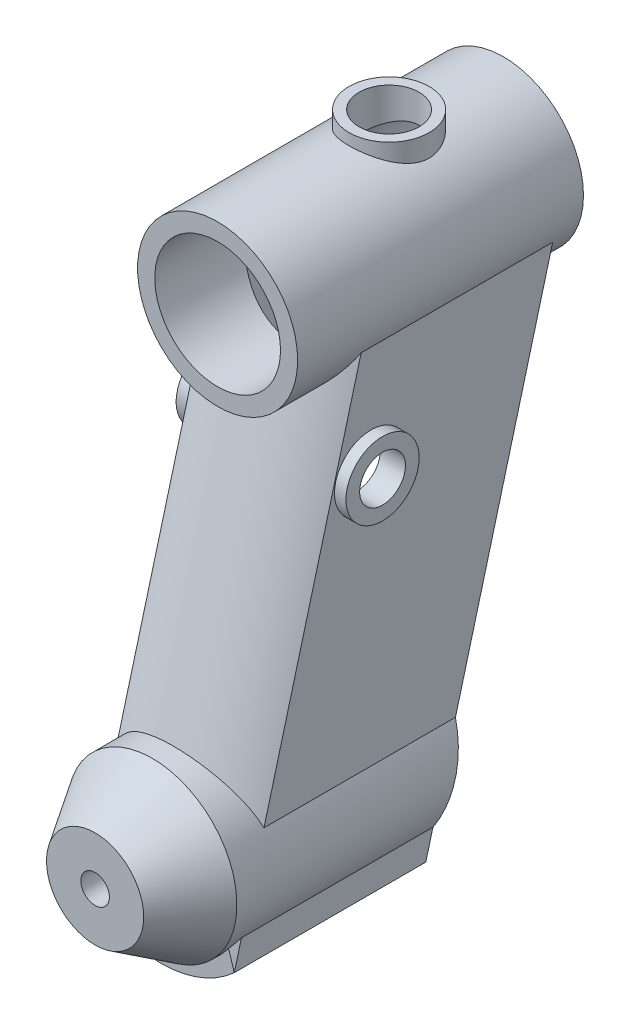
SolidWorks part; units mm, degrees
ref_plane "Front Plane" through (0, 0, 0) normal (0, 0, 1) x (1, 0, 0)
ref_plane "Top Plane" through (0, 0, 0) normal (0, 1, 0) x (1, 0, 0)
ref_plane "Right Plane" through (0, 0, 0) normal (1, 0, 0) x (0, 0, -1)
sketch "Sketch1" plane through (0, 0, 0) normal (0, 0, 1) x (1, 0, 0)
  circle A0 centre (0, 0) radius 14
  circle A1 centre (0, 0) radius 11
  dimension "D1" = 28
  dimension "D2" = 22
extrude "Boss-Extrude1" add sketch "Sketch1" along normal blind 25 and the other way blind 25
sketch "Sketch2" plane through (0, 0, 0) normal (1, 0, 0) x (0, 0, -1)
  line L0 (-25, -14) -> (25, -14) construction
  line L1 (-25, -14) -> (25, -14) construction
  line L2 (-15, -14) -> (-34.9291, -88.3763)
  line L3 (18.5, -14) -> (-1.4291, -88.3763)
  line L4 (18.5, -14) -> (18.5, -88.3763) construction
  line L5 (18.5, -88.3763) -> (-1.4291, -88.3763) construction
  line L6 (-34.9291, -88.3763) -> (-1.4291, -88.3763)
  line L7 (-15, -14) -> (18.5, -14) construction
  line L8 (-15, -14) -> (-11.2487, 0)
  line L9 (-11.2487, 0) -> (22.2513, 0)
  line L10 (22.2513, 0) -> (18.5, -14)
  dimension "D1" = 10
  dimension "D2" = 33.5
  dimension "D3" = 15
  dimension "D4" = 77
extrude "Boss-Extrude2" add sketch "Sketch2" along normal blind 12.85 and the other way blind 12.85
sketch "Sketch3" plane through (0, -88.3763, 0) normal (0, -1, 0) x (1, 0, 0)
  line L0 (-12.85, 34.9291) -> (12.85, 34.9291) construction
  line L1 (0, 34.9291) -> (0, 39.9291) construction
  line L2 (-12.85, 34.9291) -> (12.85, 34.9291)
  arc A0 (-12.85, 34.9291) -> (12.85, 34.9291) centre (0, 20.9168) cw
  dimension "D1" = 5
extrude "Boss-Extrude3" add sketch "Sketch3" along direction (0, -0.9659, 0.2588) on the side against the normal up to surface (85.7411 mm away) up to face at (0, -9.7784, -2.8812)
ref_plane "Plane1" through (0, 0, 1.4291) normal (0, 0, 1) x (1, 0, 0)
sketch "Sketch4" plane through (0, 0, 1.4291) normal (0, 0, 1) x (1, 0, 0)
  line L0 (-12.85, -88.3763) -> (12.85, -88.3763) construction
  line L1 (-12.85, -88.3763) -> (12.85, -88.3763)
  line L2 (0, -88.3763) -> (0, -93.3763) construction
  arc A0 (-12.85, -88.3763) -> (12.85, -88.3763) centre (0, -74.364) ccw
  dimension "D1" = 5
extrude "Boss-Extrude4" add sketch "Sketch4" along normal up to vertex (33.5 mm away) up to point (-12.85, -88.3763, 34.9291)
sketch "Sketch6" plane through (0, 0, 1.4291) normal (0, 0, 1) x (1, 0, 0)
  line L0 (0, -93.3763) -> (0, -74.364) construction
  arc A0 (-12.85, -88.3763) -> (12.85, -88.3763) centre (0, -74.364) ccw construction
  arc A1 (-12.85, -88.3763) -> (12.85, -88.3763) centre (0, -74.364) ccw construction
  circle A2 centre (0, -76.364) radius 14.8
  point P6 (0, -76.3948)
  point P7 (0, 0)
  dimension "D1" = 29.6
  dimension "D2" = 2
extrude "Boss-Extrude5" add sketch "Sketch6" along normal blind 35
sketch "Sketch7" plane through (0, 0, 36.4291) normal (0, 0, 1) x (1, 0, 0)
  arc A0 (10.4067, -86.8874) -> (-10.4067, -86.8874) centre (0, -76.364) ccw construction
  arc A1 (10.4067, -86.8874) -> (-10.4067, -86.8874) centre (0, -76.364) ccw construction
  circle A2 centre (0, -76.364) radius 14.8
extrude "Cut-Extrude2" cut sketch "Sketch7" along normal through all
sketch "Sketch10" plane through (0, 0, 34.9291) normal (0, 0, 1) x (1, 0, 0)
  line L0 (-12.85, -83.7069) -> (-12.85, -88.3763)
  line L1 (12.85, -83.7069) -> (12.85, -88.3763)
  arc A0 (10.4067, -86.8874) -> (-10.4067, -86.8874) centre (0, -76.364) ccw construction
  arc A1 (10.4067, -86.8874) -> (12.85, -83.7069) centre (0, -76.364) ccw
  arc A2 (-12.85, -88.3763) -> (12.85, -88.3763) centre (0, -74.364) ccw construction
  arc A3 (-12.85, -88.3763) -> (12.85, -88.3763) centre (0, -74.364) ccw
  arc A4 (-10.4067, -86.8874) -> (10.4067, -86.8874) centre (0, -76.364) ccw
  arc A5 (-12.85, -83.7069) -> (-10.4067, -86.8874) centre (0, -76.364) ccw
extrude "Cut-Extrude6" cut sketch "Sketch10" along normal up to vertex (2.9206 mm away) up to point (8.6456, -88.3763, 37.8496)
ref_plane "Plane2" through (0, 0, 46.4291) normal (0, 0, 1) x (1, 0, 0)
sketch "Sketch11" plane through (0, 0, 46.4291) normal (0, 0, 1) x (1, 0, 0)
  circle A0 centre (0, -76.364) radius 14.8 construction
  circle A1 centre (0, -76.364) radius 14.8 construction
  circle A2 centre (0, -76.364) radius 8.5
  dimension "D1" = 17
sketch "Sketch12" plane through (0, 0, 36.4291) normal (0, 0, 1) x (1, 0, 0)
  circle A0 centre (0, -76.364) radius 14.8
  dimension "D1" = 29.6
loft "Loft1" add profiles "Sketch12", "Sketch11" connector at (14.8, -76.364, 36.4291) connector at (8.5, -76.364, 46.4291)
sketch "Sketch5" plane through (0, -5.5628, -20.7607) normal (0, -0.2588, -0.9659) x (-1, 0, 0)
  line L0 (12.85, -85.7348) -> (12.85, 0.0063) construction
  line L1 (-12.85, -85.7348) -> (12.85, -85.7348)
  line L2 (-12.85, -85.7348) -> (-12.85, -99.2349)
  line L3 (-12.85, -99.2349) -> (12.85, -99.2349)
  line L4 (12.85, -85.7348) -> (12.85, -99.2349)
  ellipse E0 centre (0, -80.8705) end of major axis (-19.0122, -80.8705) minor radius 18.3644 (-12.85, -94.4052) -> (12.85, -94.4052) ccw construction
extrude "Cut-Extrude1" cut sketch "Sketch5" along normal through all
sketch "Sketch13" plane through (0, 0, 1.4291) normal (0, 0, -1) x (-1, 0, 0)
  line L1 (-12.85, -83.7069) -> (-12.85, -69.0212)
  line L2 (-12.85, -83.7069) -> (-12.85, -69.0212)
  line L3 (12.85, -69.0212) -> (12.85, -83.7069)
  line L4 (12.85, -69.0212) -> (12.85, -83.7069)
  arc A1 (-12.85, -69.0212) -> (-12.85, -83.7069) centre (0, -76.364) ccw
  arc A2 (-12.85, -69.0212) -> (-12.85, -83.7069) centre (0, -76.364) ccw
  arc A3 (12.85, -83.7069) -> (12.85, -69.0212) centre (0, -76.364) ccw
  arc A4 (12.85, -83.7069) -> (12.85, -69.0212) centre (0, -76.364) ccw
  dimension "D1" = 0
  dimension "D2" = 0
extrude "Boss-Extrude6" add sketch "Sketch13" along normal up to surface (5.1862 mm away) up to face at (0, -50.3273, -8.7661)
sketch "Sketch14" plane through (0, 0, 46.4291) normal (0, 0, 1) x (1, 0, 0)
  circle A0 centre (0, -76.364) radius 2.5
  dimension "D1" = 5
extrude "Cut-Extrude7" cut sketch "Sketch14" against normal through all
sketch "Sketch15" plane through (0, 0, 0) normal (0, 0, 1) x (1, 0, 0)
  circle A0 centre (0, 0) radius 11 construction
  circle A1 centre (0, 0) radius 11
extrude "Cut-Extrude8" cut sketch "Sketch15" against normal through all and the other way through all
sketch "Sketch16" plane through (0, -5.5628, -20.7607) normal (0, -0.2588, -0.9659) x (-1, 0, 0)
  line L0 (12.85, -65.6969) -> (12.85, 0.0063) construction
  line L1 (-12.85, -65.6969) -> (-12.85, 0.0063) construction
  line L2 (-12.85, -85.7348) -> (-12.85, -80.9007) construction
  line L3 (12.85, -85.7348) -> (12.85, -80.9007) construction
  line L4 (12.85, -65.6969) -> (12.85, 0.0063) construction
  line L5 (-12.85, -65.6969) -> (-12.85, 0.0063) construction
  line L6 (-12.85, -85.7348) -> (-12.85, -80.9007) construction
  line L7 (12.85, -85.7348) -> (12.85, -80.9007) construction
  line L8 (-10.45, -85.7348) -> (-10.45, -80.9007)
  line L9 (10.45, -85.7348) -> (10.45, -80.9007)
  line L11 (-10.45, -65.6969) -> (10.45, -65.6969) construction
  line L12 (-10.45, -65.6969) -> (-10.45, -5.6969)
  line L13 (-10.45, -5.6969) -> (10.45, -5.6969) construction
  line L14 (10.45, -65.6969) -> (10.45, -5.6969)
  arc A0 (-10.45, -85.7348) -> (10.45, -85.7348) centre (0, -72.326) ccw
  arc A1 (-10.45, -80.9007) -> (-10.45, -65.6969) centre (2.481, -73.2988) cw
  arc A2 (10.45, -80.9007) -> (10.45, -65.6969) centre (-7.5178, -73.2988) ccw
  arc A3 (-10.45, -5.6969) -> (10.45, -5.6969) centre (0, 3.6196) ccw
  ellipse E0 centre (0, -73.2988) end of major axis (0, -88.6209) minor radius 14.8 (12.85, -80.9007) -> (12.85, -65.6969) ccw construction
  ellipse E1 centre (0, -73.2988) end of major axis (0, -88.6209) minor radius 14.8 (-12.85, -65.6969) -> (-12.85, -80.9007) ccw construction
  ellipse E2 centre (0, -71.2283) end of major axis (0, -51.5453) minor radius 19.0122 (-12.85, -85.7348) -> (12.85, -85.7348) ccw construction
  ellipse E3 centre (0, -73.2988) end of major axis (0, -88.6209) minor radius 14.8 (12.85, -80.9007) -> (12.85, -65.6969) ccw construction
  ellipse E4 centre (0, -73.2988) end of major axis (0, -88.6209) minor radius 14.8 (-12.85, -65.6969) -> (-12.85, -80.9007) ccw construction
  ellipse E5 centre (0, -71.2283) end of major axis (0, -51.5453) minor radius 19.0122 (-12.85, -85.7348) -> (12.85, -85.7348) ccw construction
  ellipse E6 centre (0, 5.7591) end of major axis (0, -8.7348) minor radius 14 (-12.85, 0.0063) -> (12.85, 0.0063) ccw construction
  ellipse E7 centre (0, 5.7591) end of major axis (0, -8.7348) minor radius 14 (-12.85, 0.0063) -> (12.85, 0.0063) ccw construction
  dimension "D5" = 15
  dimension "D6" = 19.5097
  dimension "D7" = 17
  dimension "D9" = 14
  dimension "D1" = 2.4
  dimension "D2" = 2.4
  dimension "D3" = 2.4
  dimension "D4" = 2.4
  dimension "D8" = 60
extrude "Cut-Extrude9" cut sketch "Sketch16" against normal blind 30
sketch "Sketch17" plane through (0, 0, 0) normal (1, 0, 0) x (0, 0, -1)
  line L0 (-25, 0) -> (25, 0) construction
  line L1 (-25, 14) -> (-25, -14) construction
  line L2 (25, -14) -> (25, 14) construction
  line L3 (-11, -24.5) -> (-11, 0) construction
  circle A0 centre (-11, -24.5) radius 4
  dimension "D2" = 8
  dimension "D1" = 24.5
  dimension "D3" = 11
extrude "Cut-Extrude10" cut sketch "Sketch17" against normal up to surface and the other way up to surface up to face at (-12.85, -37.289, 4.4903) other way up to face at (12.85, -37.289, 4.4903)
sketch "Sketch18" plane through (12.85, 0, 0) normal (1, 0, 0) x (0, 0, -1)
  circle A0 centre (-11, -24.5) radius 4 construction
  circle A1 centre (-11, -24.5) radius 4
  circle A2 centre (-11, -24.5) radius 6.4
  dimension "D1" = 2.4
extrude "Boss-Extrude7" add sketch "Sketch18" along normal blind 2
mirror "Mirror1" about plane through (0, 0, 0) normal (1, 0, 0) of "Boss-Extrude7"
sketch "Sketch19" plane through (0, 0, 0) normal (0, 1, 0) x (1, 0, 0)
  line L0 (-14, -25) -> (14, -25) construction
  line L1 (-14, -25) -> (14, -25) construction
  line L2 (0, -25) -> (0, 25) construction
  line L3 (14, 25) -> (-14, 25) construction
  circle A0 centre (0, 5) radius 5.25
  dimension "D2" = 10.5
  dimension "D1" = 30
extrude "Cut-Extrude11" cut sketch "Sketch19" along normal through all
ref_plane "Plane3" through (0, 14, 0) normal (0, 1, 0) x (1, 0, 0)
sketch "Sketch20" plane through (0, 14, 0) normal (0, 1, 0) x (1, 0, 0)
  circle A0 centre (0, 5) radius 7
  circle A1 centre (0, 5) radius 5.25 construction
  circle A2 centre (0, 5) radius 5.25
  dimension "D1" = 14
extrude "Boss-Extrude8" add sketch "Sketch20" along normal blind 2 and the other way blind 8
sketch "Sketch21" plane through (0, 0, 0) normal (0, 0, 1) x (1, 0, 0)
  circle A0 centre (0, 0) radius 11 construction
  circle A1 centre (0, 0) radius 11
extrude "Cut-Extrude12" cut sketch "Sketch21" against normal through all and the other way through all
